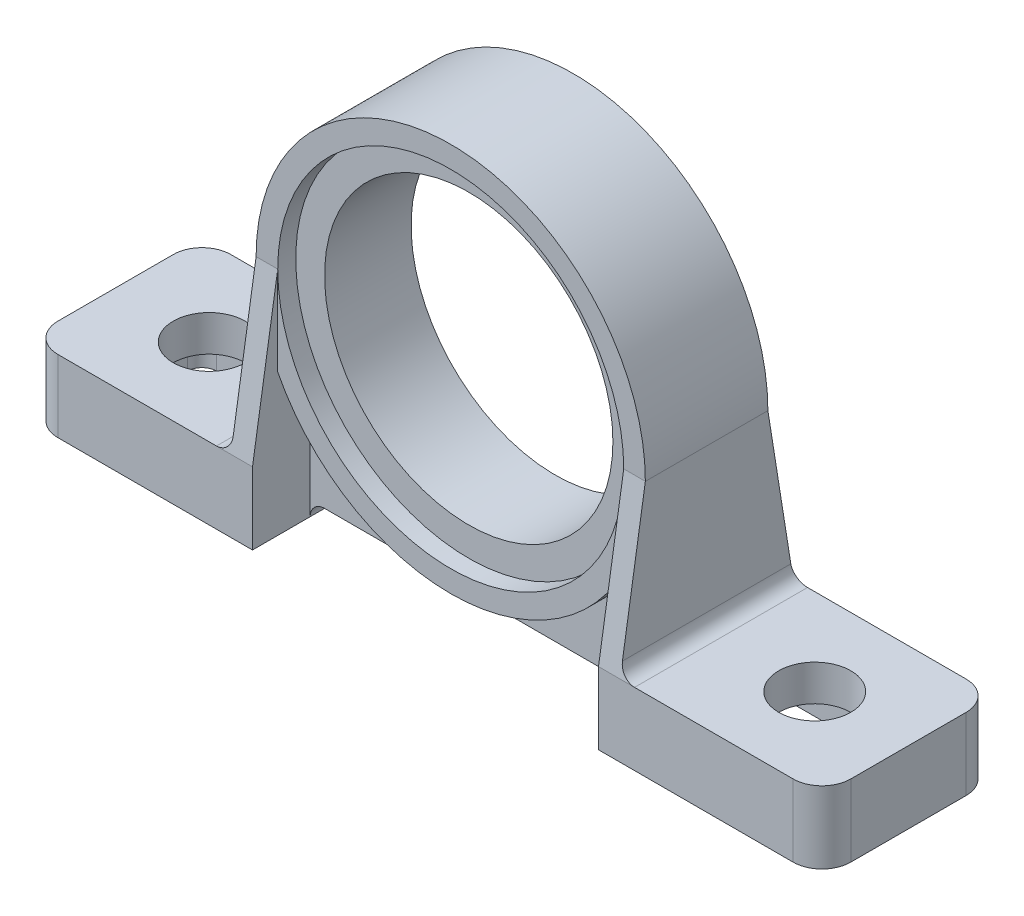
SolidWorks part; units mm, degrees
ref_plane "Front Plane" through (0, 0, 0) normal (0, 0, 1) x (1, 0, 0)
ref_plane "Top Plane" through (0, 0, 0) normal (0, 1, 0) x (1, 0, 0)
ref_plane "Right Plane" through (0, 0, 0) normal (1, 0, 0) x (0, 0, -1)
sketch "Sketch1" plane through (0, 0, 0) normal (0, 0, 1) x (1, 0, 0)
  line L0 (0, 11.0056) -> (0, -7.1043) construction
  line L1 (-13.5, 0) -> (13.5, 0) construction
  line L2 (-13.5, 0) -> (-13.5, -16) construction
  line L3 (-13.5, -16) -> (13.5, -16) construction
  line L4 (13.5, 0) -> (13.5, -16) construction
  line L5 (27.5, -16) -> (-27.5, -16)
  line L6 (-13.5, -16) -> (-27.5, -16) construction
  line L7 (-13.5, -16) -> (-13.5, -11) construction
  line L8 (-13.5, -11) -> (-27.5, -11) construction
  line L9 (-27.5, -16) -> (-27.5, -11) construction
  line L10 (-27.5, -16) -> (-27.5, -11)
  line L11 (-27.5, -11) -> (-13.5, -11)
  line L12 (-13.5, -11) -> (-13.5, 0)
  line L13 (27.5, -16) -> (27.5, -11)
  line L14 (27.5, -11) -> (13.5, -11)
  line L15 (13.5, -11) -> (13.5, 0)
  circle A0 centre (0, 0) radius 13.5 construction
  circle A1 centre (0, 0) radius 10
  arc A2 (-13.5, 0) -> (13.5, 0) centre (0, 0) cw
  point P16 (0, -16)
  dimension "D1" = 27
  dimension "D4" = 20
  dimension "D2" = 16
  dimension "D3" = 5
  dimension "D5" = 55
extrude "Boss-Extrude1" add sketch "Sketch1" along normal blind 12
ref_plane "Plane1" through (-27.5, 0, 0) normal (-1, 0, 0) x (0, 0, 1)
sketch "Sketch2" plane through (-27.5, 0, 0) normal (-1, 0, 0) x (0, 0, 1)
  line L0 (0, -11) -> (0, 0) construction
  line L1 (0, 0) -> (1.75, 0) construction
  line L2 (12, 0) -> (0, 0) construction
  line L3 (1.75, 0) -> (0, -11)
  line L4 (0, -11) -> (0, -16)
  line L5 (0, -16) -> (12, -16)
  line L6 (12, -16) -> (12, -11)
  line L7 (12, -11) -> (0, -11)
  line L8 (0, -11) -> (0, -16) construction
  line L9 (0, -16) -> (12, -16) construction
  line L10 (12, -16) -> (12, -11) construction
  line L11 (12, -11) -> (0, -11) construction
  line L12 (1.75, 0) -> (1.75, 13.5)
  line L13 (12, 13.5) -> (0, 13.5) construction
  line L14 (6, -11) -> (6, -4.8156) construction
  line L15 (0, -11) -> (12, -11)
  line L16 (1.75, 13.5) -> (10.25, 13.5)
  line L17 (10.25, 0) -> (12, -11)
  line L18 (10.25, 0) -> (10.25, 13.5)
  line L19 (0, -11) -> (0, 13.5)
  line L20 (0, 13.5) -> (0, 0) construction
  line L21 (0, 13.5) -> (12, 13.5)
  line L22 (12, 0) -> (12, 13.5) construction
  line L23 (12, 13.5) -> (12, -11)
  point P13 (6, -11)
  point P14 (6, -11)
  point P19 (6, 13.5)
  dimension "D2" = 8.5
  dimension "D1" = 0
extrude "Cut-Extrude1" cut sketch "Sketch2" against normal through all contours L23 L21 L18 L17 | L21 L19 L3 L12 region at (-27.5, 3.7346, 0.7906) region at (-27.5, 3.7346, 11.2094)
sketch "Sketch3" plane through (0, 0, 0) normal (0, 0, 1) x (1, 0, 0)
  line L0 (0, 7.0768) -> (0, -5.3488) construction
  line L1 (-12, 0) -> (-12, -16)
  line L2 (-13.5, 0) -> (-10, 0)
  line L3 (10, 0) -> (13.5, 0)
  line L4 (-13.5, 0) -> (-10, 0) construction
  line L5 (10, 0) -> (13.5, 0)
  line L6 (-27.5, -16) -> (27.5, -16) construction
  line L7 (-12, -16) -> (12, -16)
  line L8 (12, 0) -> (12, -16)
  circle A0 centre (0, 0) radius 12
  arc A3 (13.5, 0) -> (-13.5, 0) centre (0, 0) ccw
  arc A4 (10, 0) -> (-10, 0) centre (0, 0) ccw
  arc A5 (13.5, 0) -> (-13.5, 0) centre (0, 0) ccw construction
  arc A6 (10, 0) -> (-10, 0) centre (0, 0) ccw
  point P18 (0, -16)
  dimension "D2" = 1.5
  dimension "D1" = 0
extrude "Cut-Extrude2" cut sketch "Sketch3" along normal blind 4 from offset 8 contours A0 L1 L7 L8 region at (0, -12.1669, 0)
extrude "Cut-Extrude3" cut sketch "Sketch3<3>" along normal blind 4 contours A0 L1 L7 L8 region at (0, -12.1669, 0)
sketch "Sketch3<3>" plane through (0, 0, 0) normal (0, 0, 1) x (1, 0, 0) same geometry as "Sketch3"
sketch "Sketch4" plane through (0, 0, 0) normal (0, 0, 1) x (1, 0, 0)
  circle A0 centre (0, 0) radius 13.5
  circle A1 centre (0, 0) radius 12
  dimension "D1" = 27
  dimension "D2" = 24
extrude "Boss-Extrude2" add sketch "Sketch4" along normal mid plane 8.5 from offset 6
sketch "Sketch6" plane through (0, 0, 0) normal (0, 0, 1) x (1, 0, 0)
  circle A0 centre (0, 0) radius 10
  circle A1 centre (0, 0) radius 12
  dimension "D1" = 24
  dimension "D2" = 20
extrude "Cut-Extrude4" cut sketch "Sketch6" along normal blind 3
extrude "Cut-Extrude5" cut sketch "Sketch6<2>" against normal blind 3 from offset 12
sketch "Sketch6<2>" plane through (0, 0, 0) normal (0, 0, 1) x (1, 0, 0) same geometry as "Sketch6"
sketch "Sketch7" plane through (0, -16, 0) normal (0, -1, 0) x (1, 0, 0)
  line L0 (27.5, 6) -> (-27.5, 6) construction
  line L1 (0, 8) -> (0, 4) construction
  line L12 (-12, 0) -> (-12, 4)
  line L13 (-12, 4) -> (12, 4)
  line L14 (12, 4) -> (12, 0)
  line L15 (12, 0) -> (27.5, 0)
  line L16 (27.5, 0) -> (27.5, 12)
  line L17 (27.5, 12) -> (12, 12)
  line L18 (12, 12) -> (12, 8)
  line L19 (12, 8) -> (-12, 8)
  line L20 (-12, 8) -> (-12, 12)
  line L21 (-12, 12) -> (-27.5, 12)
  line L22 (-27.5, 12) -> (-27.5, 0)
  line L23 (-27.5, 0) -> (-12, 0)
  line L24 (-12, 0) -> (-12, 4) construction
  line L25 (-12, 4) -> (12, 4) construction
  line L26 (12, 4) -> (12, 0) construction
  line L27 (12, 0) -> (27.5, 0) construction
  line L28 (27.5, 0) -> (27.5, 12) construction
  line L29 (27.5, 12) -> (12, 12) construction
  line L30 (12, 12) -> (12, 8) construction
  line L31 (12, 8) -> (-12, 8) construction
  line L32 (-12, 8) -> (-12, 12) construction
  line L33 (-12, 12) -> (-27.5, 12) construction
  line L34 (-27.5, 12) -> (-27.5, 0) construction
  line L35 (-27.5, 0) -> (-12, 0) construction
  circle A0 centre (-21, 6) radius 2.5
  circle A1 centre (21, 6) radius 2.5
  dimension "D3" = 5
  dimension "D2" = 42
  dimension "D1" = 0
extrude "Cut-Extrude6" cut sketch "Sketch7" against normal up to surface (5 mm away) up to face at (-20.5, -11, 6)
sketch "Sketch8" plane through (0, -16, 0) normal (0, -1, 0) x (1, 0, 0)
  line L0 (-27.5, 6) -> (27.5, 6) construction
  line L1 (0, 8) -> (0, 4) construction
  line L2 (25, 9.5) -> (15, 9.5)
  line L3 (-25, 2.5) -> (-15, 2.5)
  line L4 (-25, 2.5) -> (-25, 9.5)
  line L5 (-25, 9.5) -> (-15, 9.5)
  line L6 (-15, 2.5) -> (-15, 9.5)
  line L7 (-25, 2.5) -> (-15, 9.5) construction
  line L8 (-25, 9.5) -> (-15, 2.5) construction
  line L9 (15, 2.5) -> (15, 9.5)
  line L10 (25, 2.5) -> (15, 2.5)
  line L11 (25, 2.5) -> (25, 9.5)
  line L12 (-12, 0) -> (-12, 4)
  line L13 (-12, 4) -> (12, 4)
  line L14 (12, 4) -> (12, 0)
  line L15 (12, 0) -> (27.5, 0)
  line L16 (27.5, 0) -> (27.5, 12)
  line L17 (27.5, 12) -> (12, 12)
  line L18 (12, 12) -> (12, 8)
  line L19 (12, 8) -> (-12, 8)
  line L20 (-12, 8) -> (-12, 12)
  line L21 (-12, 12) -> (-27.5, 12)
  line L22 (-27.5, 12) -> (-27.5, 0)
  line L23 (-27.5, 0) -> (-12, 0)
  line L24 (-12, 0) -> (-12, 4)
  line L25 (-12, 4) -> (12, 4)
  line L26 (12, 4) -> (12, 0)
  line L27 (12, 0) -> (27.5, 0)
  line L28 (27.5, 0) -> (27.5, 12)
  line L29 (27.5, 12) -> (12, 12)
  line L30 (12, 12) -> (12, 8)
  line L31 (12, 8) -> (-12, 8)
  line L32 (-12, 8) -> (-12, 12)
  line L33 (-12, 12) -> (-27.5, 12)
  line L34 (-27.5, 12) -> (-27.5, 0)
  line L35 (-27.5, 0) -> (-12, 0)
  point P6 (-20, 6)
  dimension "D2" = 7
  dimension "D3" = 10
  dimension "D4" = 30
  dimension "D1" = 0
extrude "Cut-Extrude7" cut sketch "Sketch8" against normal blind 2.5 contours L4 L3 L6 L5 | L2 L9 L10 L11
sketch "Sketch9" plane through (0, -16, 0) normal (0, -1, 0) x (1, 0, 0)
  line L1 (12, 4) -> (-12, 4)
  line L2 (12, 4) -> (12, 8)
  line L3 (12, 8) -> (-12, 8)
  line L4 (-12, 4) -> (-12, 8)
extrude "Cut-Extrude8" cut sketch "Sketch9" against normal blind 1
fillet "Fillet1" radius 1 4 edges at (13.5, -11, 6) (-13.5, -11, 6) (-12, -15, 6) (12, -15, 6)
fillet "Fillet2" radius 2 4 edges at (27.5, -13.5, 12) (27.5, -13.5, 0) (-27.5, -13.5, 0) (-27.5, -13.5, 12)
fillet "Fillet3" radius 1 8 edges at (25, -14.75, 2.5) (25, -14.75, 9.5) (15, -14.75, 2.5) (15, -14.75, 9.5) (-15, -14.75, 2.5) (-25, -14.75, 9.5) (-25, -14.75, 2.5) (-15, -14.75, 9.5)
